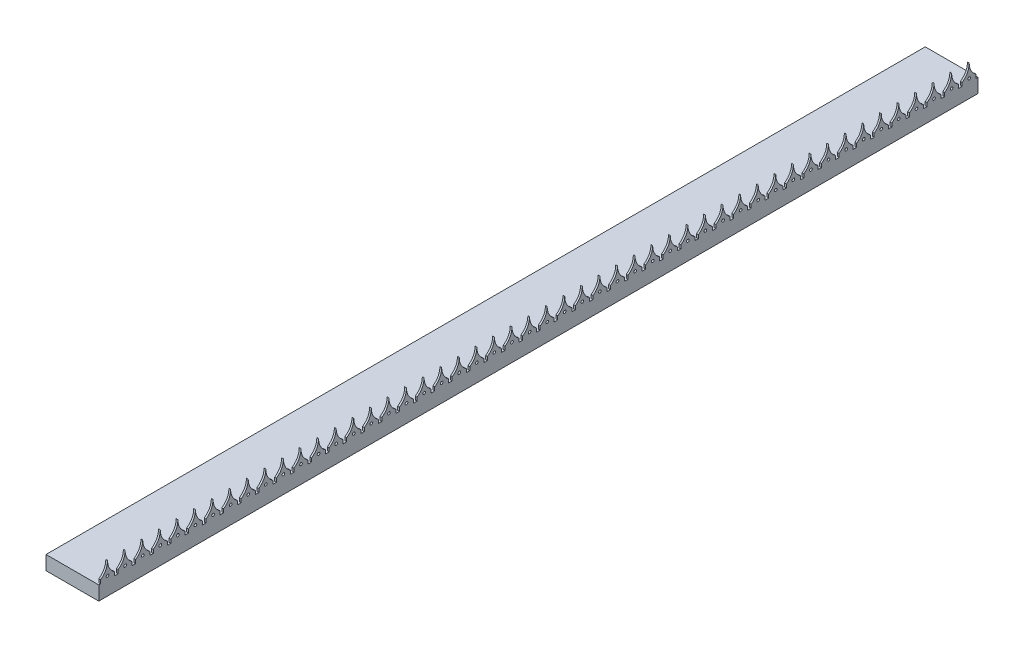
SolidWorks part; units mm, degrees
material "Plain Carbon Steel"
ref_plane "Front Plane" through (0, 0, 0) normal (0, 0, 1) x (1, 0, 0)
ref_plane "Top Plane" through (0, 0, 0) normal (0, 1, 0) x (1, 0, 0)
ref_plane "Right Plane" through (0, 0, 0) normal (1, 0, 0) x (0, 0, -1)
sketch "Sketch1" plane through (0, 0, 0) normal (0, 0, 1) x (1, 0, 0)
  line L1 (-15, -4) -> (15, -4)
  line L2 (-15, -4) -> (-15, 4)
  line L3 (-15, 4) -> (15, 4)
  line L4 (15, -4) -> (15, 4)
  line L5 (-15, -4) -> (15, 4) construction
  line L6 (-15, 4) -> (15, -4) construction
  point P0 (0, 0)
  dimension "D1" = 30
  dimension "D2" = 8
extrude "Boss-Extrude1" add sketch "Sketch1" along normal blind 10
sketch "Sketch2" plane through (15, 0, 0) normal (1, 0, 0) x (0, 0, -1)
  line L0 (-10, 4) -> (0, 4) construction
  line L1 (-9, 4) -> (-1, 4)
  line L2 (-9, 4) -> (-9, 6)
  line L3 (-9, 6) -> (-1, 6)
  line L4 (-1, 4) -> (-1, 6)
  line L5 (-9, 4) -> (-1, 6) construction
  line L6 (-9, 6) -> (-1, 4) construction
  line L7 (0, -4) -> (0, 4) construction
  line L8 (-5, 6) -> (-5, 13.8557) construction
  line L9 (-9, 6) -> (-1, 6)
  circle A0 centre (-5, 6) radius 0.75
  spline S0 degree 2 poles (-9, 6) (-4.9531, 8.8578) (-5, 13.8557) knots 0 0 0 1 1 1
  spline S1 degree 2 poles (-1, 6) (-5.0469, 8.8578) (-5, 13.8557) knots 0 0 0 1 1 1
  point P0 (-5, 5)
  line M7 (0, 4) -> (-10, 4)
  dimension "D5" = 9.2037
  dimension "D6" = 1.5
  dimension "D1" = 2
  dimension "D2" = 8
  dimension "D3" = 1
  dimension "D4" = 1
extrude "Boss-Extrude2" add sketch "Sketch2" against normal blind 1 contours L3 S1 S0 | L4 L3 L2 M7 region at (15, 4.9602, 5) region at (15, 7.8622, 5)
pattern_linear "LPattern1" count 50 spacing 10 along (0, 0, 1) of "Boss-Extrude1", "Boss-Extrude2"
